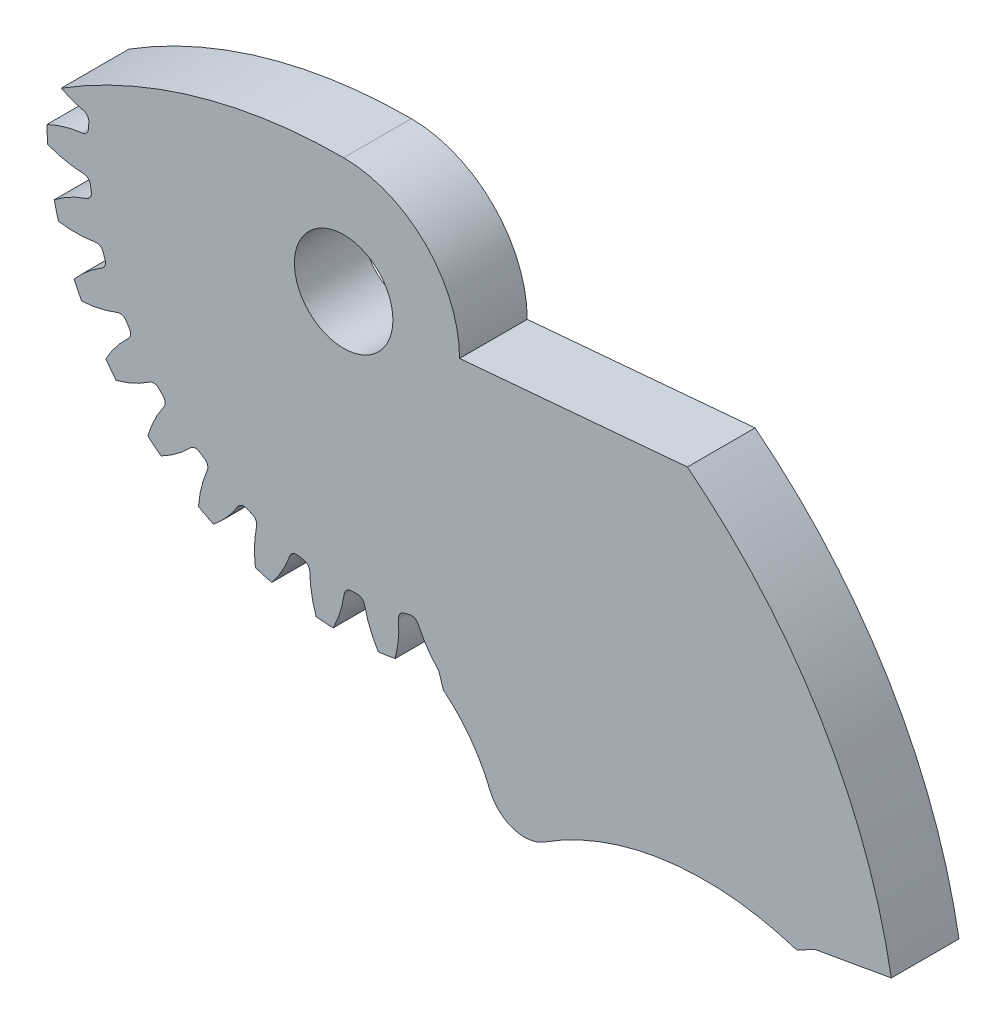
SolidWorks part; units mm, degrees
material "Delrin 2700 NC010, Low Viscosity Acetal Copolymer (SS)"
ref_plane "Front" through (0, 0, 0) normal (0, 0, 1) x (1, 0, 0)
ref_plane "Top" through (0, 0, 0) normal (0, 1, 0) x (1, 0, 0)
ref_plane "Right" through (0, 0, 0) normal (1, 0, 0) x (0, 0, -1)
sketch "Sketch3" plane through (0, 0, 0) normal (0, 0, 1) x (1, 0, 0)
  circle A0 centre (0, 0) radius 40.64
  dimension "od" = 81.28
extrude "gearBody" add sketch "Sketch3" along normal blind 25.4
sketch "Sketch2" plane through (0, 0, 0) normal (0, 0, 1) x (1, 0, 0)
  line L0 (0, 0) -> (34.0786, 14.1158) construction
  line L1 (45.4751, -11.4855) -> (0, 0) construction
  line L2 (0, 0) -> (36.3143, 0) construction
  line L3 (38.0972, -0.458) -> (37.8451, -4.4001) construction
  line L5 (37.9712, -2.4291) -> (0, 0) construction
  line L7 (0, 0) -> (36.8864, 0) construction
  arc A0 (36.879, -0.7403) -> (36.6727, -3.9649) centre (0, 0) ccw construction
  arc A1 (40.637, 0.4947) -> (40.2427, -5.6687) centre (0, 0) ccw construction
  arc A2 (38.0972, -0.458) -> (37.8451, -4.4001) centre (0, 0) ccw construction
  arc A3 (34.9015, -2.6404) -> (34.9534, -1.8283) centre (0, 0) ccw
  arc A4 (45.4751, -11.4855) -> (35.6466, -3.6712) centre (32.0022, -18.3431) ccw
  arc A5 (45.4751, -11.4855) -> (46.5679, 5.5974) centre (0, 0) ccw
  arc A6 (46.5679, 5.5974) -> (35.8238, -0.9008) centre (34.0786, 14.1158) cw
  arc A7 (34.9534, -1.8283) -> (35.8238, -0.9008) centre (35.9376, -1.8798) cw
  arc A8 (35.6466, -3.6712) -> (34.9015, -2.6404) centre (35.8842, -2.7147) cw
  point P6 (46.5679, 5.5974)
  point P22 (45.4751, -11.4855)
  dimension "baseDia" = 73.7729
  dimension "od" = 81.28
  dimension "pd" = 76.2
  dimension "rd" = 70.0024
  dimension "rFillet" = 0.9855
  dimension "pointX" = 46.5679
  dimension "pointY" = 5.5974
  dimension "CTT" = 3.9421
  dimension "flankCenterAngle" = 22.5
extrude "toothCut" cut sketch "Sketch2" along normal through all
pattern_circular "CirPattern1" count 30 over 360 about axis through (0, 0, 25.4) along (0, 0, -1) of "toothCut"
sketch "hub1Dia" plane through (0, 0, 0) normal (0, 0, -1) x (-1, 0, 0)
  circle A0 centre (0, 0) radius 12.7
  dimension "hub1Dia" = 25.4
sketch "hub2Dia" plane through (0, 0, 25.4) normal (0, 0, 1) x (1, 0, 0)
  circle A0 centre (0, 0) radius 12.7
  dimension "hub2dia" = 25.4
sketch "boreDia" plane through (0, 0, 0) normal (0, 0, 1) x (1, 0, 0)
  circle A0 centre (0, 0) radius 9.525
  dimension "boreDia" = 19.05
extrude "bore" cut sketch "boreDia" against normal mid plane 25400
sketch "Sketch4" plane through (0, 0, 25.4) normal (0, 0, 1) x (1, 0, 0)
  circle A0 centre (0, -57.15) radius 76.1746
  arc A2 (-41.7195, 6.5842) -> (41.7195, 6.5842) centre (0, 0) cw
  dimension "D1" = 152.3492
  dimension "D2" = 57.15
extrude "Cut-Extrude1" cut sketch "Sketch4" against normal through all contours A0 region at (0, 26.0638, 25.4)
sketch "Sketch5" plane through (0, 0, 25.4) normal (0, 0, 1) x (1, 0, 0)
  line L0 (0, 19.0246) -> (21.5163, 0.2011)
  line L1 (21.5163, 0.2011) -> (8.9608, -26.928)
  line L2 (8.9608, -26.928) -> (13.028, -38.4952)
  line L3 (0, 0) -> (0, -57.15) construction
  line L4 (0, -57.15) -> (-48.0548, 1.9542) construction
  line L5 (0, -57.15) -> (65.9691, -95.2373) construction
  line L6 (13.6543, -40.4261) -> (13.028, -38.4952)
  line L9 (0, -57.15) -> (75.0173, -43.9224) construction
  line L10 (75.0173, -43.9224) -> (64.5114, -45.7749)
  line L11 (64.5114, -45.7749) -> (62.0894, -47.0863)
  circle A1 centre (0, -57.15) radius 76.1746 construction
  arc A4 (33.1977, 11.4101) -> (-34.0662, 10.9827) centre (0, -57.15) ccw construction
  arc A5 (0, 19.0246) -> (75.0173, -43.9224) centre (0, -57.15) cw
  circle A6 centre (0, -57.15) radius 21.59 construction
  arc A9 (33.1977, 11.4101) -> (-34.0662, 10.9827) centre (0, -57.15) ccw construction
  arc A10 (20.0525, -49.1485) -> (13.6543, -40.4261) centre (0, -57.15) ccw
  circle A12 centre (49.4934, -85.725) radius 40.64 construction
  arc A13 (27.5177, -51.539) -> (62.0894, -47.0863) centre (49.4934, -85.725) cw
  arc A14 (27.5177, -51.539) -> (20.0525, -49.1485) centre (24.7708, -47.2658) cw
  point P12 (65.9691, -50.5109)
  point P28 (21.569, -56.1981)
  dimension "D1" = 43.18
  dimension "D3" = 81.28
  dimension "D7" = 5.08
  dimension "D2" = 120
  dimension "D4" = 57.15
  dimension "D6" = 10.668
  dimension "D5" = 80
extrude "Boss-Extrude1" add sketch "Sketch5" against normal up to surface (25.4 mm away) up to face at (9.525, 0, 0)
sketch "Sketch6" plane through (0, 0, 0) normal (0, 1, 0) x (1, 0, 0)
  line L0 (-46.1384, -9.271) -> (97.8162, -9.271)
  line L4 (97.8162, -9.271) -> (71.9328, -41.1538)
  line L5 (71.9328, -41.1538) -> (-48.6783, -38.0647)
  line L6 (-48.6783, -38.0647) -> (-46.1384, -9.271)
  dimension "D1" = 9.271
extrude "Cut-Extrude2" cut sketch "Sketch6" against normal through all both and the other way through all
sketch "Sketch7" plane through (0, 0, 9.271) normal (0, 0, 1) x (1, 0, 0)
  line L8 (15.875, 0) -> (50.2154, 3.0044)
  line L9 (-43.0106, 8.3498) -> (-40.0828, 3.8911)
  line L10 (0, -57.15) -> (-43.0106, 8.3498) construction
  line L11 (0, 0) -> (80.4469, 0) construction
  arc A0 (-40.2427, 5.6687) -> (-35.6466, 3.6712) centre (-32.0022, 18.3431) ccw construction
  circle A3 centre (0, -57.15) radius 73.025 construction
  circle A4 centre (0, 0) radius 15.875 construction
  arc A5 (0, 15.875) -> (15.875, 0) centre (0, 0) cw
  circle A8 centre (0, -57.15) radius 78.359 construction
  arc A9 (-43.0106, 8.3498) -> (50.2154, 3.0044) centre (0, -57.15) cw
  arc A10 (0, 15.875) -> (-40.0828, 3.8911) centre (0, -57.15) ccw
  point P0 (-36.4485, 3.894)
  point P11 (15.875, 0)
  point P12 (51.7246, 1.7117)
  point P14 (50.1958, 3.0207)
  dimension "D2" = 57.15
  dimension "D1" = 146.05
  dimension "D3" = 156.718
  dimension "D4" = 5
extrude "Cut-Extrude3" cut sketch "Sketch7" against normal through all both
sketch "Sketch8" plane through (0, 0, 9.271) normal (0, 0, 1) x (1, 0, 0)
  circle A0 centre (0, 0) radius 6.7469
  circle A1 centre (0, 0) radius 10.9012
  dimension "D1" = 13.4937
extrude "Boss-Extrude2" add sketch "Sketch8" against normal up to surface (9.271 mm away) up to face at (9.525, 0, 0)
equation "\"Bodytube_OD\" = 6.17in"
equation "\"Bodytube_ID\" = 5.998in"
equation "\"Fwd_Tube_Length\" = 38in"
equation "\"Mid_Tube_Length\" = 8in"
equation "\"Aft_Section_Length\"= 40in"
equation "\"Mid_Coupler_Length\" = 13in"
equation "\"Aft_Lower_Length\"= 20in"
equation "\"AB_Coupler_OD_Length\"= 1in"
equation "\"AB_Coupling_Section_Length\"= 0.375in"
equation "\"AB_Coupler_Length\"= \"AB_Coupler_OD_Length\" + \"AB_Coupling_Section_Length\" * 2"
equation "\"Cutout_Angle\" = 80"
equation "\"AB_Paddle_Height\" = 0.375in"
equation "\"AB_Coupler_Num_Screws\"= 6"
equation "\"Num_Cutouts\" = 3"
equation "\"AB_Coupler_OD\"= 6.17in"
equation "\"AB_Coupler_ID\"= 5.75in"
equation "\"AB_Coupler_Surface_Diameter\"= 5.998in"
equation "\"AB_Coupling_Screw_Diameter\"= 0.1065in"
equation "\"AB_Central_Bushing_Length\" = .75in"
equation "\"Lead_Screw_Dist\" = 2.25in"
equation "\"Lead_Screw_Diam\" = (27/64)*1in"
equation "\"Lead_Screw_Length\" = (\"Mid_Coupler_Length\" + 2*0.375in + 2*0.5in)"
equation "\"Paddle_Pin_Offset\" = .25in"
equation "\"Paddle_Pin_Radius\" = 2.25in"
equation "\"Fwd_BKHD_From_Top\" = 18in"
equation "\"D1@Sketch4\"=\"Bodytube_ID\""
equation "\"D2@Sketch4\"=\"Paddle_Pin_Radius\""
equation "\"D3@Sketch5\"=\"Paddle_Gear_OD\""
equation "\"D4@Sketch5\"=\"Paddle_Pin_Radius\""
equation "\"Motor_OD\" = 4in"
equation "\"Aft_Upper_Length\"= \"Aft_Section_Length\" - \"Aft_Lower_Length\" - \"AB_Coupler_OD_Length\""
equation "\"Paddle_Gear_OD\" = 3.2in"
equation "\"D5@Sketch5\"=\"Cutout_Angle\""
equation "\"D6@Sketch5\"=\"AB_Coupler_OD\"-\"AB_Coupler_ID\""
equation "\"D1@Sketch7\"=\"AB_Coupler_ID\""
equation "\"D2@Sketch7\"=\"Paddle_Pin_Radius\""
equation "\"D3@Sketch7\"=\"Bodytube_OD\""
